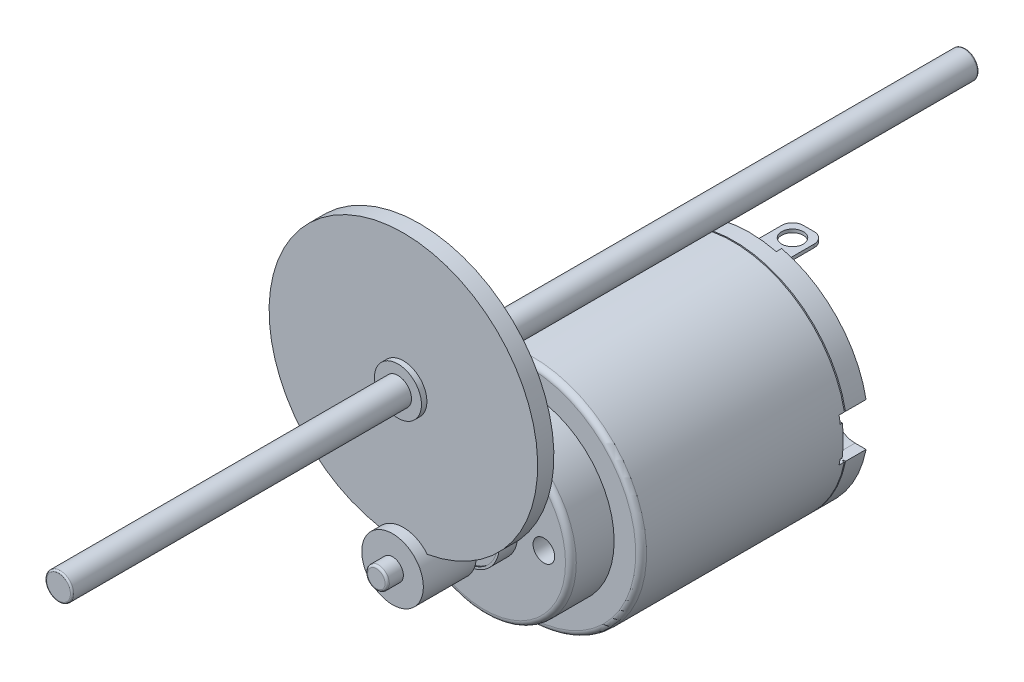
SolidWorks part; units mm, degrees
ref_plane "Plano frontal" through (0, 0, 0) normal (0, 0, 1) x (1, 0, 0)
ref_plane "Plano superior" through (0, 0, 0) normal (0, 1, 0) x (1, 0, 0)
ref_plane "Plano direito" through (0, 0, 0) normal (1, 0, 0) x (0, 0, -1)
sketch "Esboço1" plane through (0, 0, 0) normal (0, 0, 1) x (1, 0, 0)
  circle A0 centre (0, 0) radius 1
  dimension "D1" = 2
extrude "Ressalto-extrusão1" add sketch "Esboço1" along normal blind 38
ref_plane "Plano1" through (0, 0, 28) normal (0, 0, 1) x (1, 0, 0)
sketch "Esboço2" plane through (0, 0, 28) normal (0, 0, 1) x (1, 0, 0)
  circle A0 centre (0, 0) radius 8
  dimension "D1" = 16
extrude "Ressalto-extrusão2" add sketch "Esboço2" against normal blind 25
sketch "Esboço3" plane through (0, 0, 28) normal (0, 0, 1) x (1, 0, 0)
  circle A0 centre (0, 0) radius 3.075
  dimension "D1" = 6.15
extrude "Ressalto-extrusão3" add sketch "Esboço3" along normal blind 1.7
sketch "Esboço4" plane through (0, 0, 3) normal (0, 0, -1) x (-1, 0, 0)
  circle A0 centre (0, 0) radius 10.5
  dimension "D1" = 21
extrude "Ressalto-extrusão4" add sketch "Esboço4" against normal blind 21
sketch "Esboço5" plane through (0, 0, 3) normal (0, 0, -1) x (-1, 0, 0)
  circle A0 centre (0, 0) radius 3.125
  dimension "D1" = 6.25
extrude "Ressalto-extrusão5" add sketch "Esboço5" along normal blind 2
sketch "Esboço6" plane through (0, 0, 3) normal (0, 0, -1) x (-1, 0, 0)
  line L0 (0, 10.5) -> (0, -10.5) construction
  line L2 (1.5, 8.05) -> (-1.5, 8.05)
  line L3 (1.5, 8.05) -> (1.5, 7.75)
  line L4 (1.5, 7.75) -> (-1.5, 7.75)
  line L5 (-1.5, 8.05) -> (-1.5, 7.75)
  line L6 (1.5, 8.05) -> (-1.5, 7.75) construction
  line L7 (1.5, 7.75) -> (-1.5, 8.05) construction
  line L8 (1.5, -7.75) -> (-1.5, -7.75)
  line L9 (1.5, -7.75) -> (1.5, -8.05)
  line L10 (1.5, -8.05) -> (-1.5, -8.05)
  line L11 (-1.5, -7.75) -> (-1.5, -8.05)
  line L12 (1.5, -7.75) -> (-1.5, -8.05) construction
  line L13 (1.5, -8.05) -> (-1.5, -7.75) construction
  circle A0 centre (0, 0) radius 10.5 construction
  point P5 (0, 7.9)
  point P10 (0, -7.9)
  dimension "D1" = 15.5
  dimension "D2" = 0.3
  dimension "D3" = 0.3
  dimension "D4" = 3
  dimension "D5" = 3
  dimension "D6" = 7.75
extrude "Ressalto-extrusão6" add sketch "Esboço6" along normal blind 5
sketch "Esboço7" plane through (0, 8.05, 0) normal (0, 1, 0) x (1, 0, 0)
  line L0 (-1.5, 2) -> (1.5, 2) construction
  circle A0 centre (0, 0.5) radius 1
  dimension "D1" = 2
  dimension "D2" = 1.5
extrude "Corte-extrusão1" cut sketch "Esboço7" against normal blind 4
sketch "Esboço8" plane through (0, -7.75, 0) normal (0, 1, 0) x (1, 0, 0)
  circle A0 centre (0, 0.5) radius 1
extrude "Corte-extrusão2" cut sketch "Esboço8" against normal blind 4
fillet "Filete1" radius 1 4 edges at (1.5, -7.9, -2) (-1.5, -7.9, -2) (1.5, 7.9, -2) (-1.5, 7.9, -2)
fillet "Filete2" radius 0.2 2 edges at (1, 0, 0) (1, 0, 38)
sketch "Esboço9" plane through (0, 0, 3) normal (0, 0, -1) x (-1, 0, 0)
  circle A0 centre (-5.5, 0) radius 1
  circle A1 centre (5.5, 0) radius 1
  dimension "D1" = 11
  dimension "D3" = 2
  dimension "D4" = 2
  dimension "D2" = 5.5
extrude "Corte-extrusão3" cut sketch "Esboço9" against normal blind 38 and the other way blind 15
sketch "Esboço10" plane through (0, 0, 1) normal (0, 0, -1) x (-1, 0, 0)
  line L0 (2.575, 4.4181) -> (2.575, -4.909) construction
  line L2 (2.575, 4.4181) -> (2.575, -4.909)
  line L3 (2.575, -4.909) -> (3.8141, -4.909)
  line L4 (3.8141, -4.909) -> (3.8141, 4.4181)
  line L5 (3.8141, 4.4181) -> (2.575, 4.4181)
extrude "Corte-extrusão4" cut sketch "Esboço10" against normal blind 2
sketch "Esboço11" plane through (0, 0, 3) normal (0, 0, -1) x (-1, 0, 0)
  line L0 (-3.7081, 1.5) -> (-7.3485, 1.5)
  line L1 (7.3485, 1.5) -> (3.7081, 1.5)
  line L3 (7.3485, -1.5) -> (3.7081, -1.5)
  line L5 (-2.5, -7.0711) -> (-2.5, -12.5)
  line L6 (2.5, -7.0711) -> (2.5, -12.5)
  line L7 (-3.7081, -1.5) -> (-7.3485, -1.5)
  line L9 (2.5, 12.5) -> (-2.5, 12.5)
  line L10 (2.5, 12.5) -> (2.5, 7.0711)
  line L11 (2.5, -12.5) -> (-2.5, -12.5)
  line L12 (-2.5, 12.5) -> (-2.5, 7.0711)
  arc A0 (-7.3485, -1.5) -> (-2.5, -7.0711) centre (0, 0) ccw
  circle A1 centre (0, 0) radius 10.5 construction
  arc A2 (-3.7081, -1.5) -> (-2.5, -3.1225) centre (0, 0) ccw
  arc A3 (7.3485, 1.5) -> (2.5, 7.0711) centre (0, 0) ccw
  arc A4 (3.7081, 1.5) -> (2.5, 3.1225) centre (0, 0) ccw
  arc A5 (-2.5, 7.0711) -> (-7.3485, 1.5) centre (0, 0) ccw
  arc A6 (2.5, 3.1225) -> (-3.7081, 1.5) centre (0, 0) ccw
  arc A7 (2.5, -7.0711) -> (7.3485, -1.5) centre (0, 0) ccw
  arc A8 (-2.5, -3.1225) -> (3.7081, -1.5) centre (0, 0) ccw
  point P0 (0, 0)
  dimension "D2" = 3
  dimension "D3" = 8
  dimension "D1" = 5
  dimension "D4" = 25
extrude "Corte-extrusão5" cut sketch "Esboço11" against normal blind 0.5
sketch "Esboço12" plane through (0, 0, 3.5) normal (0, 0, -1) x (-1, 0, 0)
  line L0 (0, 0) -> (0, -6.6243) construction
  line L2 (0, 0) -> (13.3788, 0) construction
  arc A0 (3.375, -5.8457) -> (5.8457, -3.375) centre (0, 0) ccw
  arc A1 (2.375, -4.1136) -> (4.1136, -2.375) centre (0, 0) ccw
  arc A2 (2.375, -4.1136) -> (3.375, -5.8457) centre (2.875, -4.9796) ccw
  arc A3 (4.1136, -2.375) -> (5.8457, -3.375) centre (4.9796, -2.875) cw
  arc A8 (-3.375, 5.8457) -> (-5.8457, 3.375) centre (0, 0) ccw
  arc A9 (-4.1136, 2.375) -> (-5.8457, 3.375) centre (-4.9796, 2.875) cw
  arc A10 (-2.375, 4.1136) -> (-4.1136, 2.375) centre (0, 0) ccw
  arc A11 (-2.375, 4.1136) -> (-3.375, 5.8457) centre (-2.875, 4.9796) ccw
  dimension "D1" = 13.5
  dimension "D2" = 9.5
extrude "Corte-extrusão6" cut sketch "Esboço12" against normal blind 2
sketch "Esboço13" plane through (0, 0, 3) normal (0, 0, 1) x (1, 0, 0)
  line L1 (1.5, 8.05) -> (-1.5, 8.05)
  line L2 (1.5, 8.05) -> (1.5, 7.75)
  line L3 (1.5, 7.75) -> (-1.5, 7.75)
  line L4 (-1.5, 8.05) -> (-1.5, 7.75)
  line L5 (-1.5, -8.05) -> (1.5, -8.05)
  line L6 (-1.5, -8.05) -> (-1.5, -7.75)
  line L7 (-1.5, -7.75) -> (1.5, -7.75)
  line L8 (1.5, -8.05) -> (1.5, -7.75)
extrude "Ressalto-extrusão7" add sketch "Esboço13" along normal blind 6
ref_plane "Plano2" through (0, 0, 5) normal (0, 0, -1) x (-1, 0, 0)
sketch "Esboço14" plane through (0, 0, 5) normal (0, 0, -1) x (-1, 0, 0)
  circle A0 centre (0, 0) radius 11.3093
  circle A1 centre (0, 0) radius 10.3
  arc A2 (-2.5, 10.198) -> (-2.5, -10.198) centre (0, 0) ccw construction
  dimension "D1" = 0.2
extrude "Corte-extrusão7" cut sketch "Esboço14" along normal blind 0.1
fillet "Filete3" radius 0.5 2 edges at (8, 0, 28) (-10.5, 0, 24)
sketch "Esboço15" plane through (0, 0, 29.7) normal (0, 0, 1) x (1, 0, 0)
  circle A0 centre (0, 0) radius 2.875
  circle A1 centre (0, 0) radius 3.075 construction
  dimension "D1" = 0.2
extrude "Corte-extrusão8" cut sketch "Esboço15" against normal blind 0.1
sketch "Esboço16" plane through (0, 0, 3) normal (0, 0, -1) x (-1, 0, 0)
  line L0 (-9.2871, 2) -> (-10.3078, 2)
  line L1 (10.3078, 2) -> (9.2871, 2)
  line L3 (10.3078, -2) -> (9.2871, -2)
  line L7 (-9.2871, -2) -> (-10.3078, -2)
  arc A0 (-2.5, 10.198) -> (-2.5, -10.198) centre (0, 0) ccw construction
  arc A3 (-9.2871, -2) -> (-9.2871, 2) centre (-9.2871, 0) ccw
  arc A4 (9.2871, 2) -> (9.2871, -2) centre (9.2871, 0) ccw
  arc A5 (-10.3078, 2) -> (-10.3078, -2) centre (0, 0) ccw
  arc A6 (10.3078, -2) -> (10.3078, 2) centre (0, 0) ccw
  point P0 (0, 0)
  dimension "D1" = 4
extrude "Corte-extrusão9" cut sketch "Esboço16" against normal blind 2.5
sketch "Esboço17" plane through (0, 0, 5.5) normal (0, 0, -1) x (-1, 0, 0)
  line L0 (-8.5973, 1.3172) -> (-10.417, 1.3172)
  line L1 (10.417, 1.3172) -> (8.5973, 1.3172)
  line L2 (10.417, -1.3172) -> (10.417, -1.5)
  line L3 (10.417, -1.5) -> (8.5666, -1.5)
  line L5 (8.3688, -1.3) -> (8.3951, 1.1172)
  line L6 (10.417, -1.5) -> (10.3928, -1.4965) construction
  line L7 (-8.5973, 1.3172) -> (-8.3951, 1.1172)
  line L8 (-8.3688, -1.3) -> (-8.5666, -1.5)
  line L9 (-8.5666, -1.5) -> (-10.3923, -1.5)
  line L10 (-8.3951, 1.1172) -> (-8.3688, -1.3)
  line L11 (8.5666, -1.5) -> (8.3688, -1.3)
  line L12 (8.5973, 1.3172) -> (8.3951, 1.1172)
  arc A0 (-10.417, 1.3172) -> (-10.3923, -1.5) centre (0, 0) ccw
  arc A2 (10.3923, -1.5) -> (10.417, 1.3172) centre (0, 0) ccw
  point P0 (0, 0)
  point P6 (8.3973, 1.3172)
  point P11 (-8.3973, 1.3172)
  point P13 (-8.3666, -1.5)
  point P14 (8.3666, -1.5)
  arc M6 (-10.3078, 2) -> (-10.3078, -2) centre (0, 0) ccw
extrude "Ressalto-extrusão8" add sketch "Esboço17" along normal blind 0.2 contours L3 A2 L1 L12 L5 L11 | L10 L7 L0 L9 L8 M6 region at (9.4319, -0.0921, 5.5) region at (-9.4319, -0.0921, 5.5)
ref_plane "Plano3" through (0, 0, 36.5) normal (0, 0, 1) x (1, 0, 0)
sketch "Esboço18" plane through (0, 0, 36.5) normal (0, 0, 1) x (1, 0, 0)
  circle A0 centre (0, 0) radius 2.85
  dimension "D1" = 5.7
extrude "Ressalto-extrusão9" add sketch "Esboço18" against normal blind 4.9
ref_plane "Plano4" through (0, 0, 35.5) normal (0, 0, 1) x (1, 0, 0)
sketch "Esboço19" plane through (0, 0, 35.5) normal (0, 0, 1) x (1, 0, 0)
  line L0 (0, 0) -> (0, 14.025) construction
  line L1 (-11.4438, -2.85) -> (12.0372, -2.85) construction
  line L3 (13.7014, 26.45) -> (-10.6901, 26.45) construction
  circle A0 centre (0, 14.025) radius 12.425
  circle A2 centre (0, 0) radius 2.85 construction
  dimension "D1" = 24.85
  dimension "D2" = 29.3
extrude "Ressalto-extrusão10" add sketch "Esboço19" against normal blind 1.5
sketch "Esboço20" plane through (0, 0, 34) normal (0, 0, -1) x (-1, 0, 0)
  circle A0 centre (0, 14.025) radius 2.175
  dimension "D1" = 4.35
extrude "Ressalto-extrusão11" add sketch "Esboço20" against normal blind 2
sketch "Esboço21" plane through (0, 0, 36) normal (0, 0, 1) x (1, 0, 0)
  circle A0 centre (0, 14.025) radius 2.175
extrude "Ressalto-extrusão12" add sketch "Esboço21" against normal blind 3.9
sketch "Esboço22" plane through (0, 0, 32.1) normal (0, 0, -1) x (-1, 0, 0)
  circle A0 centre (0, 14.025) radius 1.25
  dimension "D1" = 2.5
extrude "Corte-extrusão10" cut sketch "Esboço22" against normal blind 7.9 and the other way blind 12
ref_plane "Plano5" through (0, 0, -16.5) normal (0, 0, 1) x (1, 0, 0)
sketch "Esboço23" plane through (0, 0, -16.5) normal (0, 0, 1) x (1, 0, 0)
  circle A0 centre (0, 14.025) radius 1.25
extrude "Ressalto-extrusão13" add sketch "Esboço23" along normal blind 83.9
fillet "Filete4" radius 0.15 2 edges at (1.25, 14.025, -16.5) (1.25, 14.025, 67.4)
